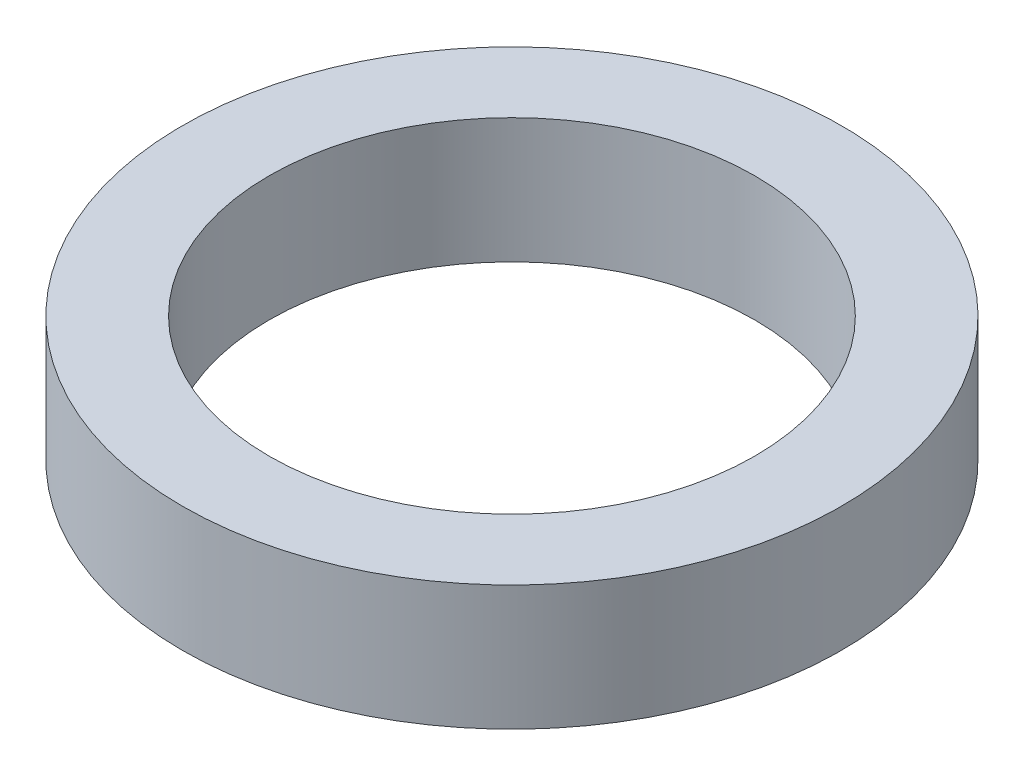
SolidWorks part; units mm, degrees
ref_plane "Front Plane" through (0, 0, 0) normal (0, 0, 1) x (1, 0, 0)
ref_plane "Top Plane" through (0, 0, 0) normal (0, 1, 0) x (1, 0, 0)
ref_plane "Right Plane" through (0, 0, 0) normal (1, 0, 0) x (0, 0, -1)
sketch "Sketch1" plane through (0, 0, 0) normal (0, 1, 0) x (1, 0, 0)
  circle A0 centre (0, 0) radius 47.5
  dimension "FLANGE_OD" = 95
extrude "Boss-Extrude1" add sketch "Sketch1" along normal blind 18
sketch "Sketch2" plane through (0, 0, 0) normal (0, 1, 0) x (1, 0, 0)
  circle A0 centre (0, 0) radius 35
  dimension "BORE_D" = 70
extrude "Cut-Extrude1" cut sketch "Sketch2" along normal through all
sketch "Sketch3" plane through (0, 18, 0) normal (0, 1, 0) x (1, 0, 0)
  circle A0 centre (0, 0) radius 22.0583 construction
  circle A1 centre (-22.0583, 0) radius 1.581
  dimension "BOLT_D" = 3.162
  dimension "BOLT_PCD" = 44.1167
extrude "Cut-Extrude2" cut sketch "Sketch3" against normal blind 11.2073 rebuild error yes
pattern_circular "CirPattern1" count 4 over 360 rebuild error yes
